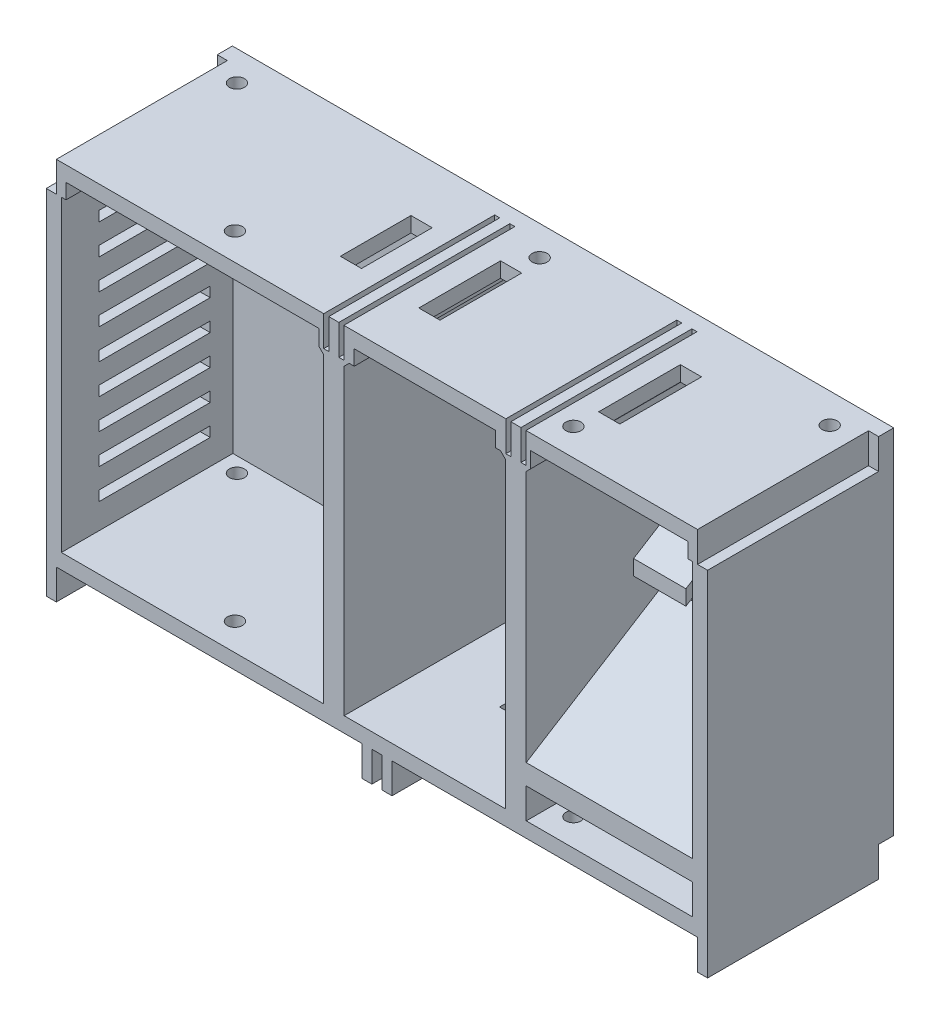
SolidWorks part; units mm, degrees
material "ABS"
ref_plane "Alzado" through (0, 0, 0) normal (0, 0, 1) x (1, 0, 0)
ref_plane "Planta" through (0, 0, 0) normal (0, 1, 0) x (1, 0, 0)
ref_plane "Vista lateral" through (0, 0, 0) normal (1, 0, 0) x (0, 0, -1)
sketch "Croquis1" plane through (0, 0, 0) normal (0, 0, 1) x (1, 0, 0)
  line L0 (0, 0) -> (2, 0)
  line L1 (2, 0) -> (2, 6)
  line L2 (55, 0) -> (55, 6)
  line L3 (55, 6) -> (2, 6)
  line L4 (56, 0) -> (56, 6)
  line L5 (56, 6) -> (58, 6)
  line L6 (58, 6) -> (58, 0)
  line L7 (58, 0) -> (59, 0)
  line L8 (59, 0) -> (59, 6)
  line L9 (91.1, 0) -> (91.1, 6)
  line L10 (59, 6) -> (91.1, 6)
  line L11 (92.1, 0) -> (92.1, 6)
  line L12 (92.1, 6) -> (94.1, 6)
  line L13 (94.1, 6) -> (94.1, 0)
  line L14 (95.1, 0) -> (95.1, 6)
  line L15 (129.1, 0) -> (129.1, 6)
  line L16 (129.1, 6) -> (95.1, 6)
  line L17 (0, 0) -> (0, -64)
  line L18 (0, -64) -> (131.1, -64)
  line L19 (131.1, -64) -> (131.1, 0)
  line L20 (55, 0) -> (56, 0)
  line L21 (58, 0) -> (59, 0)
  line L22 (129.1, 0) -> (131.1, 0)
  line L23 (94.1, 0) -> (95.1, 0)
  line L24 (91.1, 0) -> (92.1, 0)
  line L25 (2, 0) -> (129.1, 0)
  point P3 (2, 0)
  point P4 (129.1, 0)
  point P5 (55, 0)
  point P10 (56, 0)
  point P11 (58, 0)
  point P12 (59, 0)
  point P15 (91.1, 0)
  point P22 (92.1, 0)
  point P23 (94.1, 0)
  point P24 (95.1, 0)
  dimension "D1" = 131.1
  dimension "D2" = 2
  dimension "D3" = 2
  dimension "D4" = 55
  dimension "D5" = 6
  dimension "D6" = 1
  dimension "D7" = 2
  dimension "D8" = 1
  dimension "D9" = 32.1
  dimension "D10" = 1
  dimension "D11" = 2
  dimension "D12" = 1
  dimension "D13" = 64
extrude "Saliente-Extruir1" add sketch "Croquis1" along normal blind 34 contours L8 L25 L9 L10 | L1 L25 L2 L3 | L14 L25 L15 L16 | L11 L25 L13 L12 | L4 L25 L6 L5 region at (28.5, 3, 0) region at (57, 3, 0) region at (112.1, 3, 0) region at (75.05, 3, 0) region at (93.1, 3, 0)
sketch "Croquis2" plane through (0, 0, 0) normal (0, 0, 1) x (1, 0, 0)
  line L1 (2, -64) -> (129.1, -64)
  line L3 (129.1, 0) -> (2, 0)
  line L5 (129.1, 0) -> (131.1, 0)
  line L7 (129.1, -64) -> (131.1, -64)
  line L8 (131.1, 0) -> (131.1, -64)
  line L9 (2, -64) -> (0, -64)
  line L11 (2, 0) -> (0, 0)
  line L12 (0, -64) -> (0, 0)
  dimension "D1" = 64
  dimension "D2" = 2
  dimension "D3" = 2
extrude "Saliente-Extruir2" add sketch "Croquis2" along normal blind 3
sketch "Croquis3" plane through (0, 0, 3) normal (0, 0, 1) x (1, 0, 0)
  line L0 (0, -64) -> (131.1, -64) construction
  line L1 (131.1, 0) -> (128.1, 0)
  line L2 (131.1, 0) -> (131.1, -64)
  line L3 (131.1, -64) -> (128.1, -64)
  line L4 (128.1, 0) -> (128.1, -61)
  line L6 (0, 0) -> (3, 0)
  line L7 (0, 0) -> (0, -64)
  line L8 (0, -64) -> (3, -64)
  line L9 (3, 0) -> (3, -61)
  line L10 (3, -64) -> (128.1, -64)
  line L12 (3, -61) -> (128.1, -61)
  dimension "D1" = 3
  dimension "D2" = 3
  dimension "D3" = 3
extrude "Saliente-Extruir3" add sketch "Croquis3" along normal up to vertex (31 mm away) up to point (129.1, 0, 34)
sketch "Croquis4" plane through (0, 0, 0) normal (0, 0, -1) x (-1, 0, 0)
  line L24 (-59, 0) -> (-59, 6)
  line L25 (-59, 6) -> (-91.1, 6)
  line L26 (-91.1, 6) -> (-91.1, 0)
  line L27 (-91.1, 0) -> (-92.1, 0)
  line L28 (-92.1, 0) -> (-92.1, 6)
  line L29 (-92.1, 6) -> (-94.1, 6)
  line L30 (-94.1, 6) -> (-94.1, 0)
  line L31 (-94.1, 0) -> (-95.1, 0)
  line L32 (-95.1, 0) -> (-95.1, 6)
  line L33 (-95.1, 6) -> (-129.1, 6)
  line L34 (-129.1, 6) -> (-129.1, 0)
  line L35 (-129.1, 0) -> (-131.1, 0)
  line L36 (-131.1, 0) -> (-131.1, -64)
  line L37 (-131.1, -64) -> (0, -64)
  line L38 (0, -64) -> (0, 0)
  line L39 (0, 0) -> (-2, 0)
  line L40 (-2, 0) -> (-2, 6)
  line L41 (-2, 6) -> (-55, 6)
  line L42 (-55, 6) -> (-55, 0)
  line L43 (-55, 0) -> (-56, 0)
  line L44 (-56, 0) -> (-56, 6)
  line L45 (-56, 6) -> (-58, 6)
  line L46 (-58, 6) -> (-58, 0)
  line L47 (-58, 0) -> (-59, 0)
  line L48 (-59, 0) -> (-59, 6)
  line L49 (-59, 6) -> (-91.1, 6)
  line L50 (-91.1, 6) -> (-91.1, 0)
  line L51 (-91.1, 0) -> (-92.1, 0)
  line L52 (-92.1, 0) -> (-92.1, 6)
  line L53 (-92.1, 6) -> (-94.1, 6)
  line L54 (-94.1, 6) -> (-94.1, 0)
  line L55 (-94.1, 0) -> (-95.1, 0)
  line L56 (-95.1, 0) -> (-95.1, 6)
  line L57 (-95.1, 6) -> (-129.1, 6)
  line L58 (-129.1, 6) -> (-129.1, 0)
  line L59 (-129.1, 0) -> (-131.1, 0)
  line L60 (-131.1, 0) -> (-131.1, -64)
  line L61 (-131.1, -64) -> (0, -64)
  line L62 (0, -64) -> (0, 0)
  line L63 (0, 0) -> (-2, 0)
  line L64 (-2, 0) -> (-2, 6)
  line L65 (-2, 6) -> (-55, 6)
  line L66 (-55, 6) -> (-55, 0)
  line L67 (-55, 0) -> (-56, 0)
  line L68 (-56, 0) -> (-56, 6)
  line L69 (-56, 6) -> (-58, 6)
  line L70 (-58, 6) -> (-58, 0)
  line L71 (-58, 0) -> (-59, 0)
  dimension "D1" = 0
extrude "Saliente-Extruir4" add sketch "Croquis4" along normal blind 3
sketch "Croquis5" plane through (0, 0, 3) normal (0, 0, 1) x (1, 0, 0)
  line L1 (128.1, -61) -> (3, -61) construction
  line L23 (54.95, 0.05) -> (59.05, 0.05)
  line L24 (55, 0) -> (55, 6) construction
  line L25 (59, 0) -> (59, 6) construction
  line L26 (58, 0) -> (56, 0) construction
  line L27 (54.95, 0.05) -> (54.95, -61)
  line L28 (59.05, 0.05) -> (59.05, -61)
  line L29 (91.05, 0.05) -> (95.15, 0.05)
  line L30 (91.1, 0) -> (91.1, 6) construction
  line L31 (95.1, 0) -> (95.1, 6) construction
  line L32 (95.1, 0) -> (94.1, 0) construction
  line L33 (91.05, 0.05) -> (91.05, -61)
  line L34 (128.1, -61) -> (3, -61) construction
  line L35 (91.05, -61) -> (95.15, -61)
  line L36 (95.15, -61) -> (95.15, 0.05)
  line M6 (128.1, 0) -> (95.1, 0)
  line M7 (95.1, 0) -> (94.1, 0)
  line M8 (94.1, 0) -> (92.1, 0)
  line M9 (92.1, 0) -> (91.1, 0)
  line M10 (91.1, 0) -> (59, 0)
  line M11 (59, 0) -> (58, 0)
  line M12 (58, 0) -> (56, 0)
  line M13 (56, 0) -> (55, 0)
  line M14 (55, 0) -> (3, 0)
  line M16 (3, -61) -> (128.1, -61)
  dimension "D1" = 0.05
  dimension "D2" = 0.05
  dimension "D3" = 0.05
  dimension "D4" = 0.05
  dimension "D5" = 0.05
  dimension "D6" = 0.05
extrude "Saliente-Extruir10" add sketch "Croquis5" along normal up to vertex (31 mm away) contours L28 L27 M10 M11 M12 M13 M14 M16 | L36 L33 M16 M6 M7 M8 M9 M10 region at (57, -30.5, 3) region at (93.1, -30.5, 3) up to point (59, 0, 34)
sketch "Croquis6" plane through (0, 0, 0) normal (0, -1, 0) x (1, 0, 0)
  line L0 (0, 34) -> (0, -3) construction
  line L1 (0, 15.5) -> (131.1, 15.5) construction
  line L2 (131.1, 34) -> (131.1, -3) construction
  line L3 (51, 8.5) -> (51, 22.5)
  line L4 (51, 22.5) -> (46.8, 22.5)
  line L5 (46.8, 22.5) -> (46.8, 8.5)
  line L6 (46.8, 8.5) -> (51, 8.5)
  line L7 (99.1, 7.4) -> (99.1, 23.6)
  line L8 (99.1, 23.6) -> (103.3, 23.6)
  line L9 (103.3, 23.6) -> (103.3, 7.4)
  line L10 (103.3, 7.4) -> (99.1, 7.4)
  line L11 (63.45, 7.4) -> (63.45, 23.6)
  line L12 (63.45, 23.6) -> (67.65, 23.6)
  line L13 (67.65, 23.6) -> (67.65, 7.4)
  line L14 (67.65, 7.4) -> (63.45, 7.4)
  point P6 (99.1, 15.5)
  point P9 (51, 15.5)
  point P15 (99.1, 15.5)
  point P17 (63.45, 15.5)
  point P21 (63.45, 15.5)
  dimension "D1" = 51
  dimension "D2" = 4.2
  dimension "D3" = 14
  dimension "D4" = 32
  dimension "D5" = 16.2
  dimension "D6" = 4.2
  dimension "D7" = 12.45
extrude "Cortar-Extruir1" cut sketch "Croquis6" against normal up to next
sketch "Croquis7" plane through (0, 0, 34) normal (0, 0, 1) x (1, 0, 0)
  line L0 (3, 0) -> (54.95, 0) construction
  line L1 (28.975, 0) -> (28.975, 3)
  line L2 (3.925, 3) -> (54.025, 3)
  line L3 (54.025, 3) -> (54.025, 0)
  line L4 (3.925, 0) -> (54.025, 0)
  line L5 (3.925, 3) -> (3.925, 0)
  line L6 (75.05, 0) -> (75.05, 3)
  line L7 (59.05, 0) -> (91.05, 0) construction
  line L8 (75.05, 3) -> (89.05, 3)
  line L9 (89.05, 3) -> (89.05, 0)
  line L10 (89.05, 0) -> (75.05, 0)
  line L11 (75.05, 3) -> (61.05, 3)
  line L12 (61.05, 3) -> (61.05, 0)
  line L13 (61.05, 0) -> (75.05, 0)
  line L14 (61.05, 3) -> (75.05, 3)
  line L15 (111.625, 0) -> (111.625, 3)
  line L16 (95.15, 0) -> (128.1, 0) construction
  line L17 (111.625, 3) -> (127.225, 3)
  line L18 (127.225, 3) -> (127.225, 0)
  line L19 (127.225, 0) -> (111.625, 0)
  line L20 (111.625, 0) -> (96.025, 0)
  line L21 (96.025, 0) -> (96.025, 3)
  line L22 (96.025, 3) -> (111.625, 3)
  line M5 (59.05, 0) -> (91.05, 0)
  line M10 (95.15, 0) -> (128.1, 0)
  line M37 (3, 0) -> (54.95, 0)
  dimension "D1" = 25.05
  dimension "D2" = 3
  dimension "D3" = 14
  dimension "D4" = 15.6
extrude "Cortar-Extruir2" cut sketch "Croquis7" against normal up to vertex (31 mm away) contours L3 L2 L1 M37 | L2 L5 L1 M37 | L11 L12 L6 M5 | L9 L8 L6 M5 | L22 L21 L15 M10 | L18 L17 L15 M10 region at (16.45, 1.5, 34) region at (41.5, 1.5, 34) region at (68.05, 1.5, 34) region at (82.05, 1.5, 34) region at (103.825, 1.5, 34) region at (119.425, 1.5, 34) up to point (54.95, 0, 3)
sketch "Croquis22" plane through (0, 0, 3) normal (0, 0, 1) x (1, 0, 0)
  line L0 (95.15, 0) -> (95.15, -61) construction
  line L1 (95.15, -61) -> (128.1, -61) construction
  line L2 (128.1, -61) -> (128.1, 0) construction
  line L3 (128.1, 0) -> (127.225, 0) construction
  line L4 (127.225, 0) -> (127.225, 3) construction
  line L5 (127.225, 3) -> (96.025, 3) construction
  line L6 (96.025, 3) -> (96.025, 0) construction
  line L7 (96.025, 0) -> (95.15, 0) construction
  line L8 (91.05, -61) -> (91.05, 0) construction
  line L9 (91.05, 0) -> (89.05, 0) construction
  line L10 (89.05, 0) -> (89.05, 3) construction
  line L11 (89.05, 3) -> (61.05, 3) construction
  line L12 (61.05, 3) -> (61.05, 0) construction
  line L13 (61.05, 0) -> (59.05, 0) construction
  line L14 (59.05, 0) -> (59.05, -61) construction
  line L15 (59.05, -61) -> (91.05, -61) construction
  line L16 (54.95, -61) -> (54.95, 0) construction
  line L17 (54.95, 0) -> (54.025, 0) construction
  line L18 (54.025, 0) -> (54.025, 3) construction
  line L19 (54.025, 3) -> (3.925, 3) construction
  line L20 (3.925, 3) -> (3.925, 0) construction
  line L21 (3.925, 0) -> (3, 0) construction
  line L22 (3, 0) -> (3, -61) construction
  line L23 (3, -61) -> (54.95, -61) construction
  line L24 (95.15, 0) -> (95.15, -61)
  line L25 (95.15, -61) -> (128.1, -61)
  line L26 (128.1, -61) -> (128.1, 0)
  line L27 (128.1, 0) -> (127.225, 0)
  line L28 (127.225, 0) -> (127.225, 3)
  line L29 (127.225, 3) -> (96.025, 3)
  line L30 (96.025, 3) -> (96.025, 0)
  line L31 (96.025, 0) -> (95.15, 0)
  line L32 (91.05, -61) -> (91.05, 0)
  line L33 (91.05, 0) -> (89.05, 0)
  line L34 (89.05, 0) -> (89.05, 3)
  line L35 (89.05, 3) -> (61.05, 3)
  line L36 (61.05, 3) -> (61.05, 0)
  line L37 (61.05, 0) -> (59.05, 0)
  line L38 (59.05, 0) -> (59.05, -61)
  line L39 (59.05, -61) -> (91.05, -61)
  line L40 (54.95, -61) -> (54.95, 0)
  line L41 (54.95, 0) -> (54.025, 0)
  line L42 (54.025, 0) -> (54.025, 3)
  line L43 (54.025, 3) -> (3.925, 3)
  line L44 (3.925, 3) -> (3.925, 0)
  line L45 (3.925, 0) -> (3, 0)
  line L46 (3, 0) -> (3, -61)
  line L47 (3, -61) -> (54.95, -61)
extrude "Cortar-Extruir8" cut sketch "Croquis22" against normal blind 3 contours L40 L41 L42 L43 L44 L45 L46 L47 | L32 L33 L34 L35 L36 L37 L38 L39 | L24 L25 L26 L27 L28 L29 L30 L31
sketch "Croquis24" plane through (2, 0, 0) normal (-1, 0, 0) x (0, 0, 1)
  line L0 (34, 0) -> (-3, 0) construction
  line L5 (0.1, 0) -> (-4.3164, 0)
  line L6 (0.1, 0) -> (0.1, 6.5451)
  line L7 (0.1, 6.5451) -> (-4.3164, 6.5451)
  line L8 (-4.3164, 0) -> (-4.3164, 6.5451)
  line L9 (0, 0) -> (0, 8.0802) construction
  dimension "D1" = 0.1
extrude "Cortar-Extruir11" cut sketch "Croquis24" against normal through all contours L6 L5 L8 L7
sketch "Croquis25" plane through (0, 0, 0.1) normal (0, 0, -1) x (-1, 0, 0)
  line L1 (-2, 0) -> (-55, 0)
  line L2 (-2, 0) -> (-2, 6)
  line L3 (-2, 6) -> (-55, 6)
  line L4 (-55, 0) -> (-55, 6)
  line L5 (-59, 6) -> (-91.1, 6)
  line L6 (-59, 6) -> (-59, 0)
  line L7 (-59, 0) -> (-91.1, 0)
  line L8 (-91.1, 6) -> (-91.1, 0)
  line L9 (-95.1, 6) -> (-129.1, 6)
  line L10 (-95.1, 6) -> (-95.1, 0)
  line L11 (-95.1, 0) -> (-129.1, 0)
  line L12 (-129.1, 6) -> (-129.1, 0)
extrude "Saliente-Extruir15" add sketch "Croquis25" against normal blind 1
sketch "Croquis26" plane through (0, 0, 0) normal (0, 0, 1) x (1, 0, 0)
  line L0 (4, -60) -> (54.1, -60)
  line L1 (4, -60) -> (4, -4.1)
  line L2 (4, -4.1) -> (54.1, -4.1)
  line L3 (54.1, -60) -> (54.1, -4.1)
  line L4 (4, -60) -> (54.1, -4.1) construction
  line L5 (4, -4.1) -> (54.1, -60) construction
  line L6 (36.1, -45) -> (46.1, -45)
  line L7 (36.1, -45) -> (36.1, -39)
  line L8 (36.1, -39) -> (46.1, -39)
  line L9 (46.1, -45) -> (46.1, -39)
  line L10 (3, -61) -> (54.95, -61) construction
  line L11 (3, 0) -> (3, -61) construction
  line L12 (54.95, -61) -> (54.95, 0) construction
  circle A0 centre (24, -8.1) radius 1
  circle A1 centre (8, -18.9) radius 1
  circle A2 centre (24, -8.1) radius 2.5
  circle A3 centre (8, -18.9) radius 2.5
  point P0 (29.05, -32.05)
  point P5 (24, -8.1)
  point P8 (8, -18.9)
  dimension "D6" = 2
  dimension "D7" = 5
  dimension "D1" = 1
  dimension "D2" = 55.9
  dimension "D3" = 1
  dimension "D4" = 4
  dimension "D5" = 14.8
  dimension "D8" = 4
  dimension "D9" = 20
  dimension "D10" = 8
  dimension "D11" = 15
  dimension "D12" = 6
  dimension "D13" = 10
  dimension "D14" = 0.85
extrude "Saliente-Extruir16" add sketch "Croquis26" along normal blind 6 contours L6 L9 L8 L7 | A2 A0 | A3 A1 region at (41.1, -42, 0) region at (21.5707, -8.1, 0) region at (5.5707, -18.9, 0)
fillet "Redondeo1" radius 2.4 3 edges at (10.5, -18.9, 0) (26.5, -8.1, 0) (46.1, -42, 0)
chamfer "Chaflán1" distance 1 angle 45 4 edges at (54.95, 0, 17.05) (95.15, 0, 17.05) (91.05, 0, 17.05) (59.05, 0, 17.05)
sketch "Croquis10" plane through (0, 0, 0) normal (-1, 0, 0) x (0, 0, 1)
  line L0 (15.5, -64) -> (15.5, 6) construction
  line L1 (34, -64) -> (-3, -64) construction
  line L3 (4.5, -50) -> (4.5, -48)
  line L4 (4.5, -56) -> (26.5, -56)
  line L5 (4.5, -56) -> (4.5, -54)
  line L6 (4.5, -54) -> (26.5, -54)
  line L7 (26.5, -56) -> (26.5, -54)
  line L8 (4.5, -56) -> (26.5, -54) construction
  line L9 (4.5, -54) -> (26.5, -56) construction
  line L10 (4.5, -50) -> (26.5, -50)
  line L11 (26.5, -50) -> (26.5, -48)
  line L12 (4.5, -48) -> (26.5, -48)
  line L13 (4.5, -44) -> (4.5, -42)
  line L14 (4.5, -44) -> (26.5, -44)
  line L15 (26.5, -44) -> (26.5, -42)
  line L16 (4.5, -42) -> (26.5, -42)
  line L17 (4.5, -38) -> (4.5, -36)
  line L18 (4.5, -38) -> (26.5, -38)
  line L19 (26.5, -38) -> (26.5, -36)
  line L20 (4.5, -36) -> (26.5, -36)
  line L21 (4.5, -32) -> (4.5, -30)
  line L22 (4.5, -32) -> (26.5, -32)
  line L23 (26.5, -32) -> (26.5, -30)
  line L24 (4.5, -30) -> (26.5, -30)
  line L25 (4.5, -26) -> (4.5, -24)
  line L26 (4.5, -26) -> (26.5, -26)
  line L27 (26.5, -26) -> (26.5, -24)
  line L28 (4.5, -24) -> (26.5, -24)
  line L29 (4.5, -20) -> (4.5, -18)
  line L30 (4.5, -20) -> (26.5, -20)
  line L31 (26.5, -20) -> (26.5, -18)
  line L32 (4.5, -18) -> (26.5, -18)
  line L33 (4.5, -14) -> (4.5, -12)
  line L34 (4.5, -14) -> (26.5, -14)
  line L35 (26.5, -14) -> (26.5, -12)
  line L36 (4.5, -12) -> (26.5, -12)
  line L37 (4.5, -8) -> (4.5, -6)
  line L38 (4.5, -8) -> (26.5, -8)
  line L39 (26.5, -8) -> (26.5, -6)
  line L40 (4.5, -6) -> (26.5, -6)
  point P6 (15.5, -55)
  dimension "D1" = 22
  dimension "D2" = 2
  dimension "D3" = 8
  dimension "D4" = 9
extrude "Cortar-Extruir3" cut sketch "Croquis10" against normal up to vertex (3 mm away) contours L4 L7 L6 L5 | L12 L3 L10 L11 | L16 L13 L14 L15 | L20 L17 L18 L19 | L24 L21 L22 L23 | L28 L25 L26 L27 | L32 L29 L30 L31 | L36 L33 L34 L35 | L40 L37 L38 L39 region at (0, -49, 15.5) region at (0, -55, 15.5) region at (0, -43, 15.5) region at (0, -37, 15.5) region at (0, -31, 15.5) region at (0, -25, 15.5) region at (0, -19, 15.5) region at (0, -13, 15.5) region at (0, -7, 15.5) up to point (3, -61, 34)
sketch "Croquis12" plane through (95.15, 0, 0) normal (1, 0, 0) x (0, 0, -1)
  line L0 (0, -29.7544) -> (-34, -51)
  line L1 (0, 0) -> (0, -61) construction
  line L2 (-34, -61) -> (-34, -1) construction
  line L4 (-34, -51) -> (-34, -55)
  line L5 (-34, -55) -> (0, -33.7544)
  line L6 (0, -29.7544) -> (0, -33.7544)
  dimension "D1" = 4
  dimension "D2" = 58
  dimension "D3" = 6
extrude "Saliente-Extruir12" add sketch "Croquis12" along normal up to surface (32.95 mm away) up to face at (128.1, -24.4, 13.62)
sketch "Croquis13" plane through (95.15, 0, 0) normal (1, 0, 0) x (0, 0, -1)
  line L0 (0, -29.7544) -> (0, -21.6544) construction
  line L2 (0, -21.6544) -> (-12.7207, -29.6032)
  line L4 (0, -29.7544) -> (-34, -51) construction
  line L6 (-12.7207, -26.6032) -> (0, -18.6544)
  line L7 (0, -18.6544) -> (0, -21.6544)
  line L8 (-12.7207, -29.6032) -> (-12.7207, -26.6032)
  line L9 (-34, -51) -> (-8.7351, -35.2127) construction
  line L10 (0, -29.7544) -> (-34, -51) construction
  line L11 (-6.7844, -33.9938) -> (-6.7844, -25.8938)
  line L12 (-6.7844, -33.9938) -> (0, -29.7544)
  line L13 (0, 0) -> (0, -29.7544) construction
  line M8 (-34, -51) -> (0, -29.7544)
  line M18 (0, -29.7544) -> (0, 0)
  dimension "D1" = 8.1
  dimension "D2" = 3
  dimension "D3" = 15
  dimension "D4" = 8
extrude "Saliente-Extruir17" add sketch "Croquis13" along normal up to surface (32.95 mm away) contours L11 L2 M8 M18 | L8 L2 L6 M18 region at (95.15, -27.8241, 3.3922) region at (95.15, -24.1288, 6.3604) up to face at (128.1, -16.1509, 13.62)
ref_plane "Plano1" through (0, -18.6544, 0) normal (0, -1, 0) x (-1, 0, 0)
sketch "Croquis38" plane through (0, -18.6544, 0) normal (0, -1, 0) x (-1, 0, 0)
  line L0 (-111.625, 0) -> (-111.625, -34.0311) construction
  line L1 (-128.1, 0) -> (-95.15, 0) construction
  line L2 (-111.625, 0) -> (-117.725, 0)
  line L3 (-117.725, 0) -> (-117.725, -26)
  line L4 (-117.725, -26) -> (-105.525, -26)
  line L5 (-111.625, 0) -> (-105.525, 0)
  line L6 (-105.525, 0) -> (-105.525, -26)
  dimension "D1" = 6.1
  dimension "D2" = 6.1
  dimension "D3" = 26
  dimension "D4" = 26
extrude "Cortar-Extruir12" cut sketch "Croquis38" along normal up to vertex (15.3394 mm away) contours L0 L2 L3 L4 | L5 L0 L4 L6 region at (108.575, -18.6544, 13) region at (114.675, -18.6544, 13) up to point (128.1, -33.9938, 6.7844)
sketch "Croquis40" plane through (0, 3, 0) normal (0, -1, 0) x (1, 0, 0)
  line L0 (0, 34) -> (0, -3) construction
  line L1 (3.925, 34) -> (54.025, 34) construction
  line L2 (131.1, 34) -> (131.1, -3) construction
  line L3 (0, -3) -> (131.1, -3) construction
  circle A0 centre (32, 28.6) radius 1.5
  circle A1 centre (99.1, 28.6) radius 1.5
  circle A2 centre (6.8, 3) radius 1.5
  circle A3 centre (124.3, 3) radius 1.5
  circle A4 centre (66.8, 3) radius 1.5
  dimension "D3" = 3
  dimension "D1" = 32
  dimension "D2" = 5.4
  dimension "D4" = 32
  dimension "D5" = 6.8
  dimension "D6" = 6
  dimension "D7" = 6.8
  dimension "D8" = 60
extrude "Cortar-Extruir13" cut sketch "Croquis40" against normal up to next
sketch "Croquis42" plane through (0, 0, 0) normal (0, -1, 0) x (1, 0, 0)
  line L0 (90.05, 0.1) -> (90.05, 34) construction
  line L1 (96.15, 0.1) -> (127.225, 0.1)
  line L2 (96.15, 0.1) -> (96.15, 1.1)
  line L3 (96.15, 1.1) -> (127.225, 1.1)
  line L4 (127.225, 0.1) -> (127.225, 1.1)
  line L5 (60.05, 0.1) -> (90.05, 0.1)
  line L6 (60.05, 0.1) -> (60.05, 1.1)
  line L7 (60.05, 1.1) -> (90.05, 1.1)
  line L8 (90.05, 0.1) -> (90.05, 1.1)
  line L9 (3, 34) -> (3, 0.1) construction
  line L10 (3, 1.1) -> (53.8965, 1.1)
  line L11 (3, 1.1) -> (3, 0)
  line L12 (3, 0) -> (53.8965, 0)
  line L13 (53.8965, 1.1) -> (53.8965, 0)
  line L14 (54.95, 0) -> (3, 0) construction
extrude "Saliente-Extruir18" add sketch "Croquis42" along normal blind 0.2
sketch "Croquis44" plane through (0, 0, 0) normal (0, 0, 1) x (1, 0, 0)
  line L0 (90.05, -0.2) -> (60.05, -0.2) construction
  line L1 (62.35, -22.2) -> (87.75, -22.2)
  line L2 (62.35, -22.2) -> (62.35, -56)
  line L3 (62.35, -56) -> (87.75, -56)
  line L4 (87.75, -22.2) -> (87.75, -56)
  line L5 (59.05, -1) -> (59.05, -61) construction
  line L6 (59.05, -61) -> (91.05, -61) construction
  line L7 (75.05, -56) -> (75.05, -22.2) construction
  line L8 (62.35, -39.1) -> (87.75, -39.1) construction
  circle A0 centre (65.65, -53.7) radius 2.5
  circle A1 centre (65.65, -53.7) radius 1.2
  circle A2 centre (84.25, -53.7) radius 2.5
  circle A3 centre (84.25, -53.7) radius 1.2
  circle A4 centre (84.75, -24.2) radius 2.5
  circle A5 centre (84.75, -24.2) radius 1.2
  circle A6 centre (65.35, -24.2) radius 2.5
  circle A7 centre (65.35, -24.2) radius 1.2
  point P6 (75.05, -0.2)
  point P7 (75.05, -22.2)
  point P8 (75.05, -56)
  dimension "D4" = 5
  dimension "D5" = 2.4
  dimension "D1" = 25.4
  dimension "D2" = 33.8
  dimension "D3" = 5
  dimension "D6" = 3.3
  dimension "D7" = 2.3
  dimension "D8" = 2.3
  dimension "D9" = 3.5
  dimension "D10" = 3
  dimension "D11" = 2
  dimension "D12" = 3
  dimension "D13" = 2
extrude "Saliente-Extruir19" add sketch "Croquis44" along normal blind 3 contours L3 A2 | L3 A2 A3 | L3 A0 | L3 A0 A1 | L1 A6 A7 | L1 A6 | L1 A4 A5 | L1 A4 region at (65.35, -21.9982, 0) region at (65.35, -22.2673, 0) region at (64.3097, -51.6722, 0) region at (65.65, -56.0803, 0) region at (84.75, -21.9982, 0) region at (84.75, -22.2673, 0) region at (82.9097, -51.6722, 0) region at (84.25, -56.0803, 0)
fillet "Redondeo2" radius 3 4 edges at (86.75, -53.7, 0) (68.15, -53.7, 0) (87.25, -24.2, 0) (67.85, -24.2, 0)
sketch "Croquis48" plane through (0, 0, 0) normal (-1, 0, 0) x (0, 0, 1)
  line L1 (-3, 0) -> (0.1, 0)
  line L2 (-3, 0) -> (-3, 6)
  line L3 (-3, 6) -> (0.1, 6)
  line L4 (0.1, 0) -> (0.1, 6)
extrude "Saliente-Extruir20" add sketch "Croquis48" against normal up to vertex (131.1 mm away) up to point (131.1, 0, -3)
sketch "Croquis49" plane through (0, 0, 34) normal (0, 0, 1) x (1, 0, 0)
  line L0 (2, 0) -> (2, -64) construction
  line L1 (0, -64) -> (131.1, -64) construction
  line L2 (129.1, 0) -> (129.1, -64) construction
  line L3 (66.55, -70) -> (66.55, -64)
  line L4 (2, -64) -> (0, -64)
  line L5 (0, -64) -> (0, -70)
  line L6 (0, -70) -> (2, -70)
  line L7 (2, -70) -> (2, -64)
  line L8 (129.1, -64) -> (131.1, -64)
  line L9 (131.1, -64) -> (131.1, -70)
  line L10 (131.1, -70) -> (129.1, -70)
  line L11 (129.1, -70) -> (129.1, -64)
  line L12 (65.55, -64) -> (68.55, -64)
  line L13 (68.55, -64) -> (68.55, -70)
  line L14 (68.55, -70) -> (66.55, -70)
  line L15 (62.55, -70) -> (62.55, -64)
  line L16 (62.55, -64) -> (65.55, -64)
  line L17 (64.55, -70) -> (64.55, -64)
  line L18 (64.55, -70) -> (62.55, -70)
  dimension "D1" = 6
  dimension "D2" = 3
  dimension "D3" = 2
  dimension "D4" = 2
extrude "Saliente-Extruir21" add sketch "Croquis49" against normal up to vertex (33.9 mm away) contours L6 L7 L4 L5 | L18 L17 L16 L15 | L14 L13 L12 L3 | L11 L10 L9 L8 region at (63.55, -67, 34) region at (67.55, -67, 34) region at (1, -67, 34) region at (130.1, -67, 34) up to point (2, 0, 0.1)
sketch "Croquis50" plane through (0, -64, 0) normal (0, -1, 0) x (1, 0, 0)
  circle A0 centre (124.3, 3) radius 1.5 construction
  circle A1 centre (99.1, 28.6) radius 1.5 construction
  circle A3 centre (6.8, 3) radius 1.5 construction
  circle A4 centre (32, 28.6) radius 1.5 construction
  circle A5 centre (124.3, 3) radius 1.5
  circle A6 centre (99.1, 28.6) radius 1.5
  circle A8 centre (6.8, 3) radius 1.5
  circle A9 centre (32, 28.6) radius 1.5
extrude "Cortar-Extruir14" cut sketch "Croquis50" against normal up to surface (3 mm away) up to face at (28.975, -61, 17)
sketch "Croquis51" plane through (0, 0, 0) normal (-1, 0, 0) x (0, 0, 1)
  line L0 (0.1, -64) -> (-3, -64) construction
  line L1 (-3, 6) -> (-2.9, 6)
  line L2 (-3, 6) -> (-3, -64)
  line L3 (-3, -64) -> (-2.9, -64)
  line L4 (-2.9, 6) -> (-2.9, -64)
  dimension "D1" = 0.1
extrude "Cortar-Extruir15" cut sketch "Croquis51" against normal through all
sketch "Croquis52" plane through (0, -64, 0) normal (0, -1, 0) x (1, 0, 0)
  line L0 (68.55, 0.1) -> (68.55, 34) construction
  line L1 (72.95, 17.1) -> (78.95, 17.1)
  line L2 (72.95, 17.1) -> (72.95, 9.1)
  line L3 (72.95, 9.1) -> (78.95, 9.1)
  line L4 (78.95, 17.1) -> (78.95, 9.1)
  line L5 (131.1, -2.9) -> (0, -2.9) construction
  dimension "D1" = 4.4
  dimension "D2" = 12
  dimension "D3" = 8
  dimension "D4" = 6
extrude "Cortar-Extruir16" cut sketch "Croquis52" against normal up to vertex (3 mm away) up to point (59.05, -61, 34)
